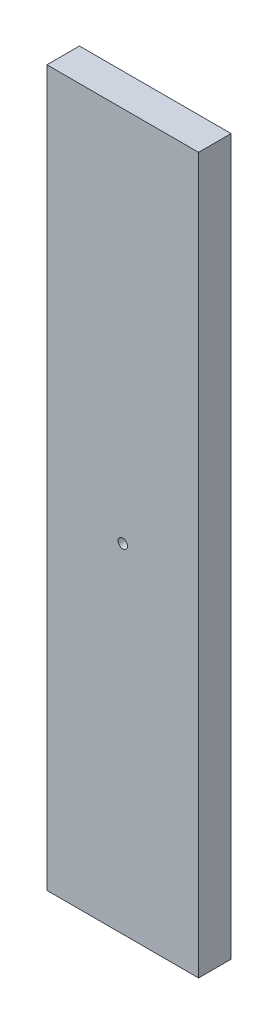
SolidWorks part; units mm, degrees
ref_plane "Front Plane" through (0, 0, 0) normal (0, 0, 1) x (1, 0, 0)
ref_plane "Top Plane" through (0, 0, 0) normal (0, 1, 0) x (1, 0, 0)
ref_plane "Right Plane" through (0, 0, 0) normal (1, 0, 0) x (0, 0, -1)
sketch "Sketch1" plane through (0, 0, 0) normal (0, 1, 0) x (1, 0, 0)
  line L1 (0, 0) -> (88.9, 0)
  line L2 (0, 0) -> (0, 19.05)
  line L3 (0, 19.05) -> (88.9, 19.05)
  line L4 (88.9, 0) -> (88.9, 19.05)
  dimension "D1" = 19.05
  dimension "D2" = 88.9
extrude "Boss-Extrude1" add sketch "Sketch1" along normal blind 419.1
sketch "Sketch2" plane through (0, 0, 0) normal (0, 0, 1) x (1, 0, 0)
  line L0 (44.45, 419.1) -> (44.45, 198.3208) construction
  line L1 (0, 419.1) -> (88.9, 419.1) construction
  line L2 (-349.25, 253.6518) -> (44.45, 198.3208) construction
  line L3 (-349.25, 253.6518) -> (-39.4224, 253.6518) construction
  circle A0 centre (44.45, 198.3208) radius 2.7781
  circle A1 centre (-349.25, 253.6518) radius 2.7781 construction
  circle A2 centre (-349.25, 253.6518) radius 2.7781 construction
  dimension "D1" = 5.5562
  dimension "D2" = 8
extrude "Cut-Extrude1" cut sketch "Sketch2" against normal through all
equation "\"DROPANGLE\" = 10"
